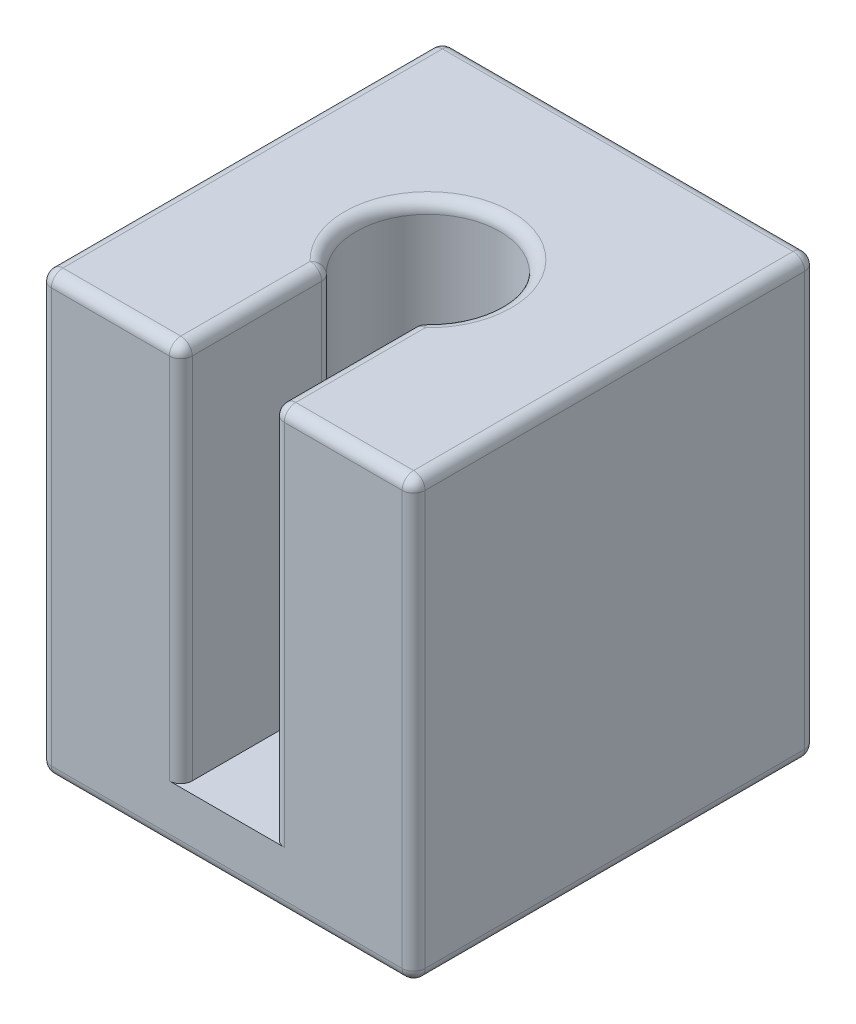
SolidWorks part; units mm, degrees
ref_plane "Front Plane" through (0, 0, 0) normal (0, 0, 1) x (1, 0, 0)
ref_plane "Top Plane" through (0, 0, 0) normal (0, 1, 0) x (1, 0, 0)
ref_plane "Right Plane" through (0, 0, 0) normal (1, 0, 0) x (0, 0, -1)
sketch "Sketch1" plane through (0, 0, 0) normal (0, 1, 0) x (1, 0, 0)
  line L1 (0, 0) -> (65, 0)
  line L2 (0, 0) -> (0, 70)
  line L3 (0, 70) -> (65, 70)
  line L4 (65, 0) -> (65, 70)
  dimension "D1" = 65
  dimension "D2" = 70
extrude "Boss-Extrude1" add sketch "Sketch1" along normal blind 76
sketch "Sketch2" plane through (0, 76, 0) normal (0, 1, 0) x (1, 0, 0)
  line L0 (-974.2368, 35) -> (49025.7632, 35) construction
  line L1 (32.5, -965.5506) -> (32.5, 49034.4494) construction
  line L2 (65, 70) -> (0, 70) construction
  line L3 (65, 0) -> (65, 70) construction
  line L4 (24.5, 0) -> (24.5, 25.3953)
  line L5 (0, 0) -> (65, 0) construction
  line L6 (40.5, 0) -> (40.5, 25.3953)
  line L7 (24.5, 0) -> (40.5, 0)
  arc A2 (40.5, 25.3953) -> (24.5, 25.3953) centre (32.5, 35) ccw
  dimension "D3" = 12.5
  dimension "D1" = 35
  dimension "D2" = 32.5
  dimension "D4" = 8
  dimension "D5" = 8
extrude "Cut-Extrude1" cut sketch "Sketch2" against normal blind 66
fillet "Fillet1" radius 2 19 edges at (24.5, 76, -12.6977) (12.25, 76, 0) (0, 76, -35) (65, 76, -35) (52.75, 76, 0) (40.5, 76, -12.6977) (32.5, 76, -47.5) (65, 38, -70) (32.5, 76, -70) (0, 38, -70) (32.5, 0, -70) (24.5, 43, 0) (40.5, 43, 0) (40.5, 43, -25.3953) (24.5, 43, -25.3953) (0, 0, -35) (0, 38, 0) (32.5, 0, 0) (65, 38, 0)
fillet "Fillet2" radius 2 3 edges at (64.4142, 0.5858, -0.5858) (64.4142, 0.5858, -69.4142) (65, 0, -35)
